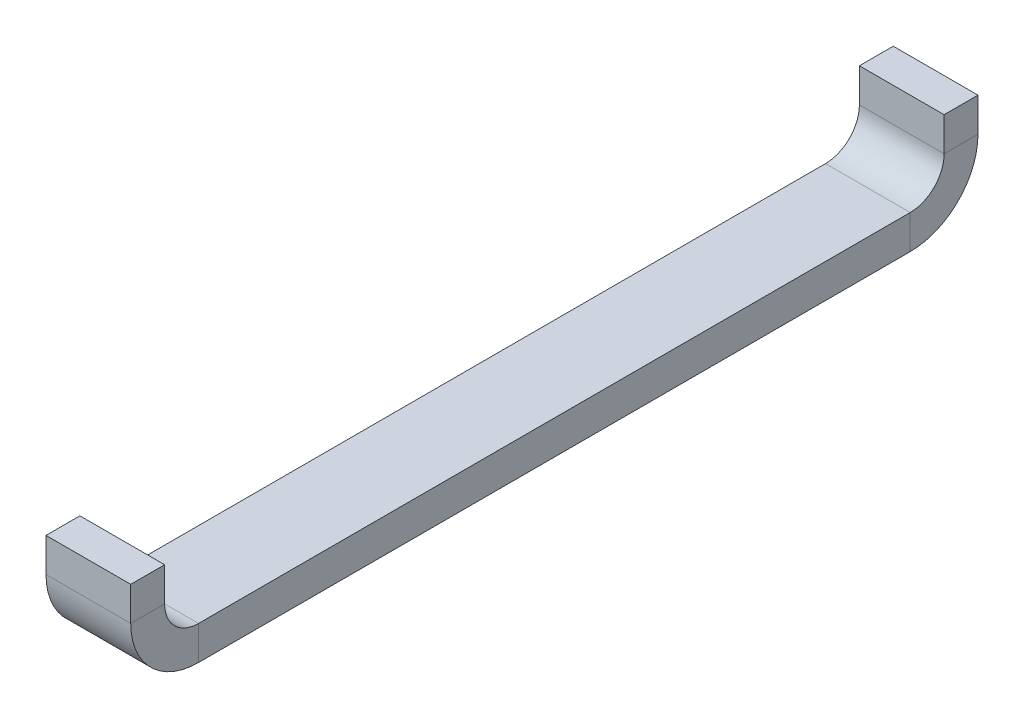
SolidWorks part; units mm, degrees
note: The reader was unsure of these and kept them because the rebuilt part matched: flange length of "Tôle pliée sur arête1".
ref_plane "Plan de face" through (0, 0, 0) normal (0, 0, 1) x (1, 0, 0)
ref_plane "Plan de dessus" through (0, 0, 0) normal (0, 1, 0) x (1, 0, 0)
ref_plane "Plan de droite" through (0, 0, 0) normal (1, 0, 0) x (0, 0, -1)
sketch "Esquisse2" plane through (0, 0, 0) normal (0, 1, 0) x (1, 0, 0)
  line L1 (0, 0) -> (5, 0)
  line L2 (0, 0) -> (0, 50)
  line L3 (0, 50) -> (5, 50)
  line L4 (5, 0) -> (5, 50)
  dimension "D1" = 50
  dimension "D2" = 5
sheet metal parameters "Tôlerie 1" thickness 2 parameters "D1"=2
base flange "Tôle de base pliée1" sketch "Esquisse2" thickness 2 reverse thickness direction no parameters "D1"=2
edge flange "Tôle pliée sur arête1" sketch "Esquisse7" flange profiles "Esquisse7", "Esquisse9" flange angle 90 flange length 6 flange position material inside bend radius 2 thickness 2 relief rectangular parameters "D6"=10, "D8"=1
sketch "Esquisse7" plane through (0, 0, 0) normal (0, 0, 1) x (1, 0, 0)
  line L0 (0, 0) -> (5, 0) construction
  line L1 (0, 0) -> (5, 0)
  line L2 (0, 0) -> (0, 4)
  line L3 (0, 4) -> (5, 4)
  line L4 (5, 4) -> (5, 0)
sketch "Esquisse9" plane through (0, 0, -50) normal (0, 0, -1) x (-1, 0, 0)
  line L0 (-5, 0) -> (0, 0) construction
  line L1 (-5, 0) -> (0, 0)
  line L2 (-5, 0) -> (-5, 4)
  line L3 (-5, 4) -> (0, 4)
  line L4 (0, 4) -> (0, 0)
bend "Pli d'arête1" bend radius 2 bend angle 90 parameters "D5"=1
bend "Pli d'arête2" bend radius 2 bend angle 90 parameters "D5"=2
flat pattern "Etat déplié1" [suppressed]
sketch "Lignes de pliage1" plane through (0, 0, 0) normal (0, 1, 0) x (1, 0, 0)
sketch3d "Cube de visualisation1" [suppressed]
  line L0 (-650, 50, 0) -> (0, 50, 0) construction
  line L1 (-650, 0, 0) -> (0, 0, 0) construction
  line L2 (-650, 50, 0) -> (-650, 0, 0) construction
  line L3 (0, 50, 0) -> (0, 0, 0) construction
bend of the flat pattern "Dépliage-<Pli d'arête1>1"
bend of the flat pattern "Dépliage-<Pli d'arête2>1"
